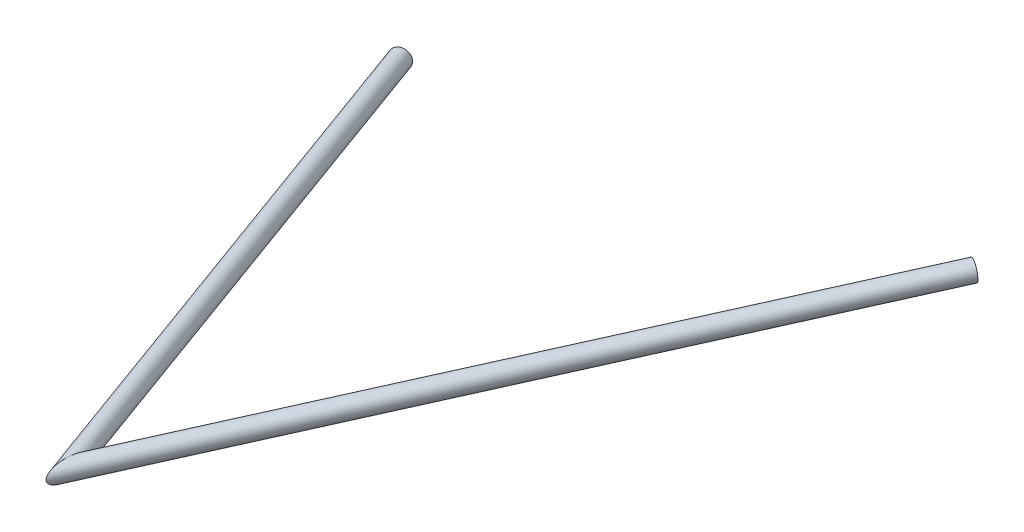
SolidWorks part; units mm, degrees
note: '?' marks a value the reader was unsure of.
material "AISI 4130 Steel, annealed at 865C"
ref_plane "Front Plane" through (0, 0, 0) normal (0, 0, 1) x (1, 0, 0)
ref_plane "Top Plane" through (0, 0, 0) normal (0, 1, 0) x (1, 0, 0)
ref_plane "Right Plane" through (0, 0, 0) normal (1, 0, 0) x (0, 0, -1)
sketch3d "reference sketch"
  line L2 (-182.037, -70.9562, -535.0595) -> (35.3236, -44.7643, 16.419)
  line L3 (35.3236, -44.7643, 16.419) -> (362.1561, -1.1688, -570.0336)
sketch3d "3DSketch2"
  line L0 (-182.037, -70.9562, -535.0595) -> (35.3236, -44.7643, 16.419)
  line L1 (35.3236, -44.7643, 16.419) -> (362.1561, -1.1688, -570.0336)
  line L2 (362.1561, -1.1688, -570.0336) -> (-182.037, -70.9562, -535.0595) construction
  point P6 (92.1631, -70.9562, -535.0595)
other "Pipe standard s40 PIPE 1 SCH 40(1)" corner treatment miter
ref_plane "Plane1" through (-182.037, -70.9562, -535.0595) normal (0.3663, 0.0441, 0.9294) x (0.9304, -0.0084, -0.3663)
sketch "Sketch1" plane through (-182.037, -70.9562, -535.0595) normal (0.3663, 0.0441, 0.9294) x (0.9304, -0.0084, -0.3663)
  circle A0 centre (0, 0) radius 8.525
  circle A1 centre (0, 0) radius 9.525
  point P3 (0, 0)
  dimension "D1" = 19.05
  dimension "D2" = 1
ref_axis "pivot axis" through (362.1561, -1.1688, -570.0336) along (-0.9899, -0.1269, 0.0636)?
ref_point "Point2"
ref_point "upright mounting point"
sketch "Sketch3" plane through (0, 0, 0) normal (1, 0, 0) x (0, 0, -1)
  circle A0 centre (570.0336, -1.1688) radius 12.7
  dimension "D1" = 25.4
